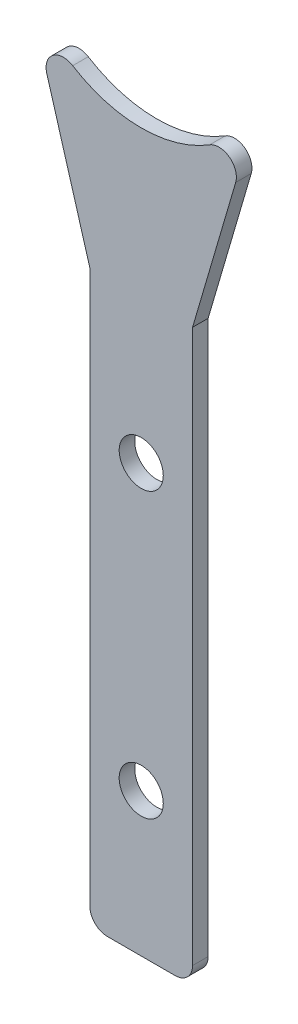
SolidWorks part; units mm, degrees
material "Custom Plastic"
ref_plane "X-Y Datum" through (0, 0, 0) normal (0, 0, 1) x (1, 0, 0)
ref_plane "X-Z Datum" through (0, 0, 0) normal (0, 1, 0) x (1, 0, 0)
ref_plane "Y-Z Datum" through (0, 0, 0) normal (1, 0, 0) x (0, 0, -1)
sketch "Sketch1" plane through (0, 0, 0) normal (0, 0, 1) x (1, 0, 0)
  line L0 (2.16, -14.0069) -> (2.16, -28.6179)
  line L2 (-3.0789, -28.6179) -> (-3.0789, 29.5681)
  line L5 (-3.0789, -28.6179) -> (7.3993, -28.6179)
  line L6 (-3.0789, 29.5681) -> (2.16, 29.5681)
  line L7 (7.3993, -28.6179) -> (7.3993, 14.5674)
  line L8 (-3.0789, 29.5681) -> (-9.5797, 51.7194)
  line L9 (7.3993, 14.5674) -> (7.3993, 29.5674)
  line L11 (7.3993, 29.5674) -> (13.8976, 51.7194)
  circle A5 centre (2.159, 57.7781) radius 13.21
  circle A6 centre (2.16, 14.9571) radius 2
  circle A7 centre (2.16, -14.0069) radius 2
  point P0 (0, 0)
  dimension "D1" = 26.42
  dimension "D2" = 4
  dimension "D3" = 4
  dimension "D6" = 28.21
  dimension "D4" = 28.964
  dimension "D5" = 14.611
extrude "Boss-Extrude1" add sketch "Sketch1" along normal blind 1.5875 contours L2 L7 region at (2.1601, 12.1893, 0)
fillet "Fillet2" radius 1.778 4 edges at (7.3993, -28.6179, 0.7937) (-3.0789, -28.6179, 0.7937) (-9.5797, 51.7194, 0.7937) (13.8976, 51.7194, 0.7937)
hole_wizard "M4 Clearance Hole2" positions "Sketch4" profile "Sketch5" hole size "M4" standard "ANSI Metric" end condition through all
sketch "Sketch4" plane through (0, 0, 1.5875) normal (0, 0, 1) x (1, 0, 0)
  point P0 (2.16, 14.9571)
  point P3 (2.16, -14.0069)
sketch "Sketch5" plane through (2.16, 14.9571, 1.5875) normal (1, 0, 0) x (0, -1, 0)
  line L0 (0, 0) -> (0, 1.5875)
  line L1 (0, 1.5875) -> (2.25, 1.5875)
  line L2 (2.25, 1.5875) -> (2.25, 0)
  line L5 (2.25, 0) -> (0, 0)
  line L11 (0, -6.35) -> (0, 107.95) construction
  dimension "Thru Hole Dia." = 4.5
  dimension "Thru Hole Depth" = 1.5875
